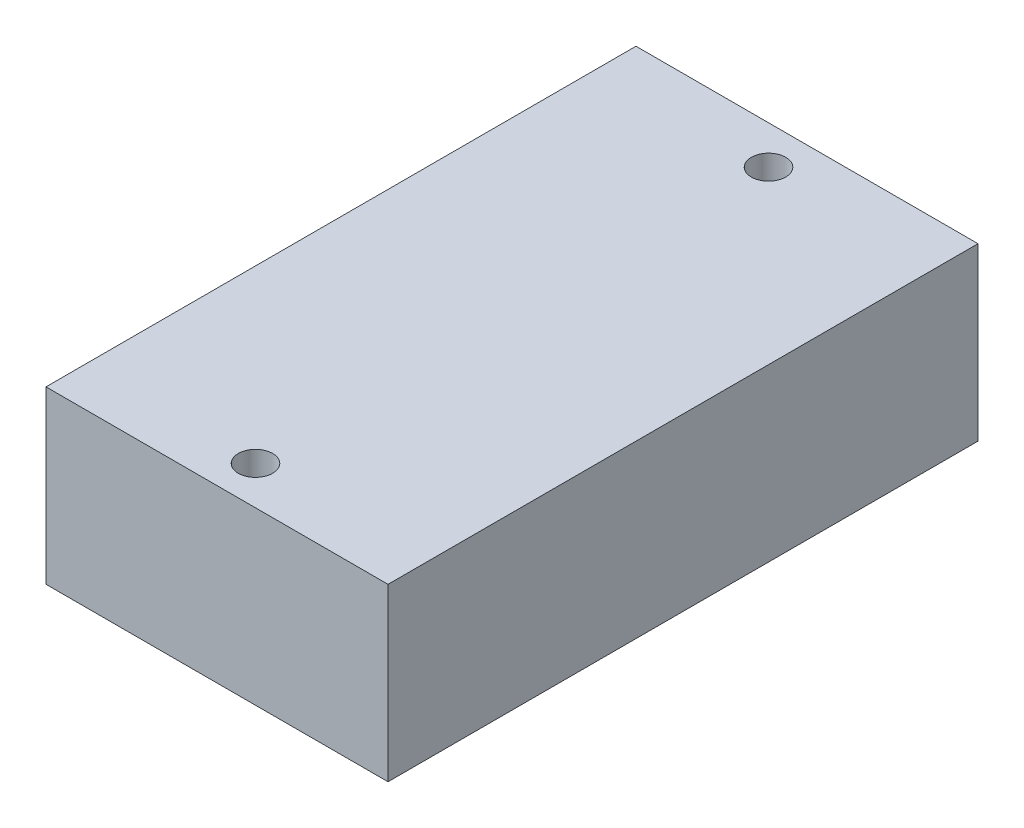
SolidWorks part; units mm, degrees
ref_plane "Front Plane" through (0, 0, 0) normal (0, 0, 1) x (1, 0, 0)
ref_plane "Top Plane" through (0, 0, 0) normal (0, 1, 0) x (1, 0, 0)
ref_plane "Right Plane" through (0, 0, 0) normal (1, 0, 0) x (0, 0, -1)
sketch "Sketch1" plane through (0, 0, 0) normal (0, 1, 0) x (1, 0, 0)
  line L1 (-25.4, 43.815) -> (25.4, 43.815)
  line L2 (-25.4, 43.815) -> (-25.4, -43.815)
  line L3 (-25.4, -43.815) -> (25.4, -43.815)
  line L4 (25.4, 43.815) -> (25.4, -43.815)
  line L5 (-25.4, 43.815) -> (25.4, -43.815) construction
  line L6 (-25.4, -43.815) -> (25.4, 43.815) construction
  point P0 (0, 0)
  dimension "D1" = 50.8
  dimension "D2" = 87.63
extrude "Boss-Extrude1" add sketch "Sketch1" along normal blind 25.4
hole_wizard "#10 Clearance Hole1" positions "Sketch2" profile "Sketch3" hole size "#10" standard "ANSI Inch" end condition through all
sketch "Sketch2" plane through (0, 25.4, 0) normal (0, 1, 0) x (1, 0, 0)
  line L0 (0, 0) -> (0, 38.1) construction
  line L2 (0, 0) -> (0, -38.1) construction
  point P2 (0, 38.1)
  point P8 (0, -38.1)
  dimension "D1" = 38.1
  dimension "D2" = 38.1
sketch "Sketch3" plane through (0, 25.4, 38.1) normal (1, 0, 0) x (0, 0, 1)
  line L0 (0, 0) -> (0, 25.4)
  line L1 (0, 25.4) -> (2.5527, 25.4)
  line L2 (2.5527, 25.4) -> (2.5527, 0)
  line L5 (2.5527, 0) -> (0, 0)
  line L11 (0, -6.35) -> (0, 107.95) construction
  dimension "Thru Hole Dia." = 5.1054
  dimension "Thru Hole Depth" = 25.4
